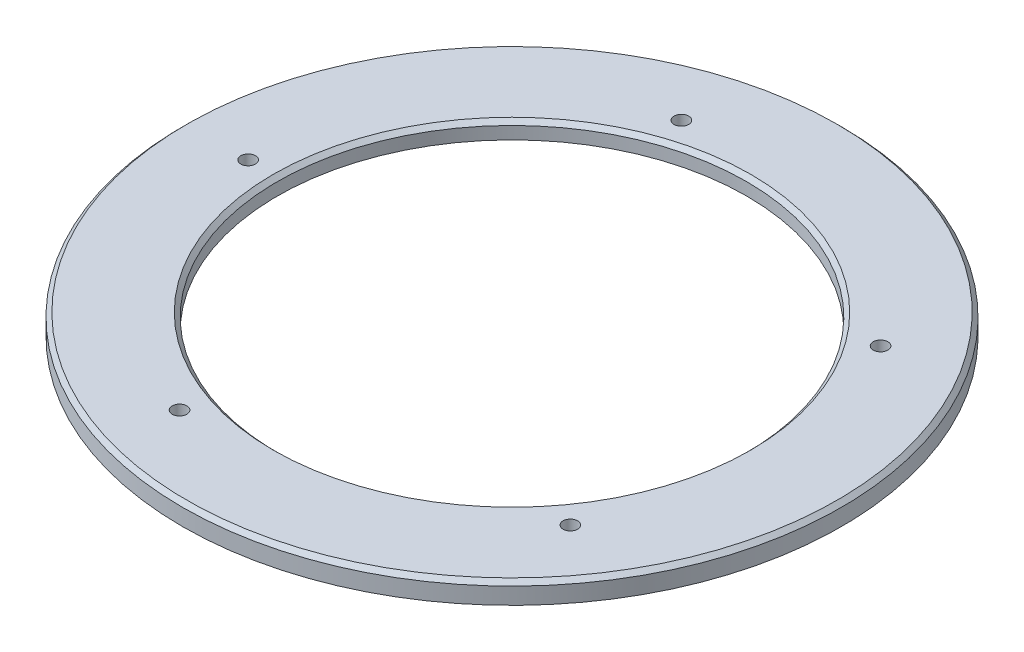
SolidWorks part; units mm, degrees
ref_plane "Front Plane" through (0, 0, 0) normal (0, 0, 1) x (1, 0, 0)
ref_plane "Top Plane" through (0, 0, 0) normal (0, 1, 0) x (1, 0, 0)
ref_plane "Right Plane" through (0, 0, 0) normal (1, 0, 0) x (0, 0, -1)
sketch "Sketch1" plane through (0, 0, 0) normal (0, 0, 1) x (1, 0, 0)
  line L0 (-70.25, 1) -> (-70.25, 0)
  line L1 (-70.25, 0) -> (-79, 0)
  line L2 (-79, 0) -> (-79, 5)
  line L3 (-79, 5) -> (-56.25, 5)
  line L4 (-56.25, 5) -> (-56.25, 1)
  line L5 (-56.25, 1) -> (-70.25, 1)
  line L6 (0, 0) -> (0, 4.4576) construction
  point P9 (0, 0)
  dimension "D1" = 1
  dimension "D2" = 158
  dimension "D3" = 140.5
  dimension "D4" = 14
  dimension "D5" = 4
revolve "Revolve1" add sketch "Sketch1" angle 360 about L6
sketch "Sketch2" plane through (0, 1, 0) normal (0, -1, 0) x (1, 0, 0)
  line L0 (-70.25, 0) -> (-56.25, 0) construction
  circle A0 centre (-63.25, 0) radius 1.7521
  circle A1 centre (0, 0) radius 70.25 construction
  circle A2 centre (0, 0) radius 56.25 construction
  circle A3 centre (-19.5453, 60.1543) radius 1.7521
  circle A4 centre (51.1703, 37.1774) radius 1.7521
  circle A5 centre (51.1703, -37.1774) radius 1.7521
  circle A6 centre (-19.5453, -60.1543) radius 1.7521
  point P9 (-63.25, 0)
  point P10 (0, 0)
  point P17 (0, 0)
  point P20 (0, 0)
  point P23 (0, 0)
  point P26 (0, 0)
  point P27 (0, 0)
  dimension "D1" = 3.5042
  dimension "D2" = 5
extrude "Cut-Extrude2" cut sketch "Sketch2" against normal through all
chamfer "Chamfer1" distance 1 angle 45 2 edges at (0, 5, -79) (0, 5, -56.25)
